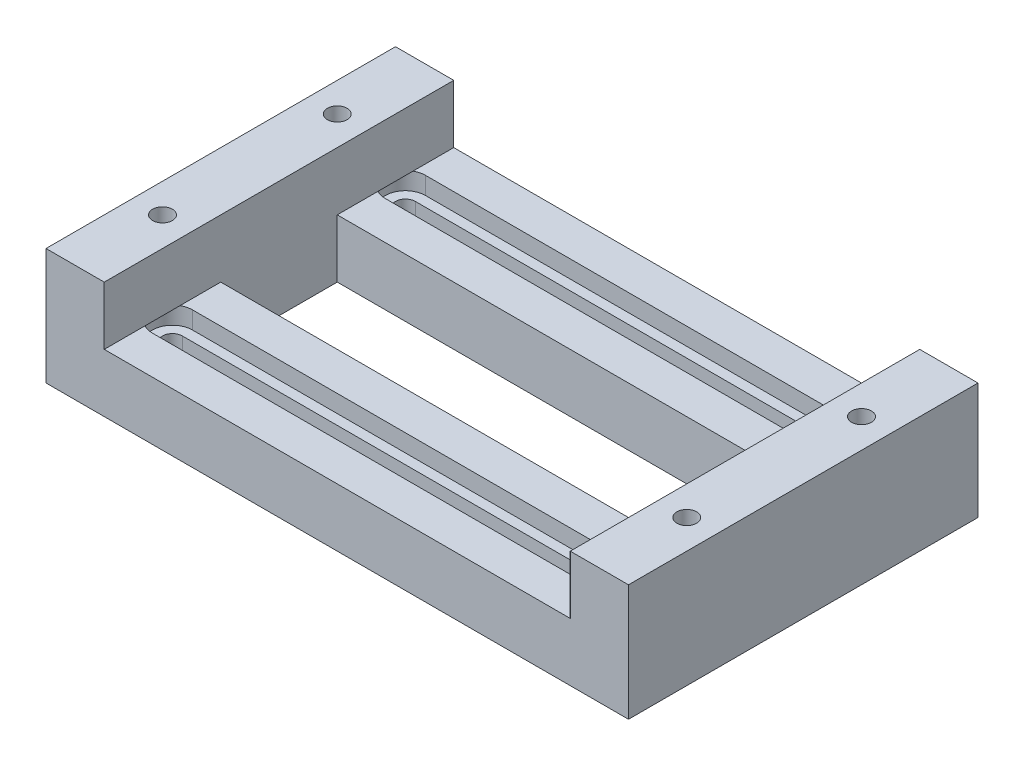
SolidWorks part; units mm, degrees
ref_plane "Front Plane" through (0, 0, 0) normal (0, 0, 1) x (1, 0, 0)
ref_plane "Top Plane" through (0, 0, 0) normal (0, 1, 0) x (1, 0, 0)
ref_plane "Right Plane" through (0, 0, 0) normal (1, 0, 0) x (0, 0, -1)
sketch "Sketch1" plane through (0, 0, 0) normal (0, 1, 0) x (1, 0, 0)
  line L0 (10, 40) -> (10, 20)
  line L1 (0, 0) -> (100, 0)
  line L2 (0, 0) -> (0, 60)
  line L3 (0, 60) -> (100, 60)
  line L4 (100, 0) -> (100, 60)
  line L5 (10, 20) -> (90, 20)
  line L6 (90, 20) -> (90, 40)
  line L7 (90, 40) -> (10, 40)
  line L8 (11.7, 10) -> (88.3, 10) construction
  line L9 (11.7, 11.7) -> (88.3, 11.7)
  line L10 (11.7, 8.3) -> (88.3, 8.3)
  line L11 (88.3, 50) -> (11.7, 50) construction
  line L12 (88.3, 48.3) -> (11.7, 48.3)
  line L13 (50, 0) -> (50, 20) construction
  line L14 (50, 40) -> (50, 60)
  line L15 (88.3, 51.7) -> (11.7, 51.7)
  circle A7 centre (5, 45) radius 1.7
  arc A22 (11.7, 11.7) -> (11.7, 8.3) centre (11.7, 10) ccw
  arc A23 (88.3, 8.3) -> (88.3, 11.7) centre (88.3, 10) ccw
  arc A24 (88.3, 48.3) -> (88.3, 51.7) centre (88.3, 50) ccw
  arc A25 (11.7, 51.7) -> (11.7, 48.3) centre (11.7, 50) ccw
  circle A29 centre (5, 15) radius 1.7
  circle A46 centre (95, 45) radius 1.7
  circle A47 centre (95, 15) radius 1.7
  point P14 (50, 50)
  point P17 (50, 10)
  point P22 (50, 50)
  point P33 (50, 10)
  point P34 (90, 10)
  point P35 (10, 10)
  point P36 (90, 50)
  point P37 (10, 50)
  dimension "D25" = 3.4
  dimension "D4" = 3.4
  dimension "D18" = 3.4
  dimension "D19" = 3.4
  dimension "D1" = 60
  dimension "D2" = 100
  dimension "D3" = 10
  dimension "D22" = 20
  dimension "D23" = 20
  dimension "D24" = 10
  dimension "D28" = 15
  dimension "D5" = 15
  dimension "D6" = 5
  dimension "D8" = 5
  dimension "D9" = 15
  dimension "D13" = 5
  dimension "D16" = 5
  dimension "D17" = 15
  dimension "D7" = 3.4
  dimension "D10" = 3.4
  dimension "D11" = 80
  dimension "D12" = 80
extrude "Boss-Extrude1" add sketch "Sketch1" along normal blind 10 contours L1 L4 L3 L2 A47 A46 A29 A7 L7 L6 L5 L0 region at (75, 0, -58.8338)
sketch "Sketch3" plane through (0, 10, 0) normal (0, 1, 0) x (1, 0, 0)
  line L4 (88.3, 53.45) -> (11.7, 53.45)
  line L5 (11.7, 46.55) -> (88.3, 46.55)
  line L6 (88.3, 13.45) -> (11.7, 13.45)
  line L7 (11.7, 6.55) -> (88.3, 6.55)
  line L8 (88.3, 13.45) -> (11.7, 13.45)
  line L9 (11.7, 6.55) -> (88.3, 6.55)
  line L10 (88.3, 53.45) -> (11.7, 53.45)
  line L11 (11.7, 46.55) -> (88.3, 46.55)
  arc A4 (88.3, 46.55) -> (88.3, 53.45) centre (88.3, 50) ccw
  arc A5 (11.7, 53.45) -> (11.7, 46.55) centre (11.7, 50) ccw
  arc A6 (11.7, 13.45) -> (11.7, 6.55) centre (11.7, 10) ccw
  arc A7 (88.3, 6.55) -> (88.3, 13.45) centre (88.3, 10) ccw
  arc A8 (11.7, 13.45) -> (11.7, 6.55) centre (11.7, 10) ccw
  arc A9 (88.3, 6.55) -> (88.3, 13.45) centre (88.3, 10) ccw
  arc A10 (88.3, 46.55) -> (88.3, 53.45) centre (88.3, 50) ccw
  arc A11 (11.7, 53.45) -> (11.7, 46.55) centre (11.7, 50) ccw
  dimension "D1" = 1.75
  dimension "D2" = 1.75
extrude "Cut-Slot insets" cut sketch "Sketch3" against normal blind 3
sketch "Sketch5" plane through (0, 10, 0) normal (0, 1, 0) x (1, 0, 0)
  line L2 (0, 60) -> (100, 60) construction
  line L3 (10, 60) -> (0, 60)
  line L4 (0, 60) -> (0, 0)
  line L5 (0, 0) -> (10, 0)
  line L6 (0, 0) -> (100, 0) construction
  line L9 (90, 0) -> (100, 0)
  line L10 (100, 0) -> (100, 60)
  line L11 (100, 60) -> (90, 60)
  line L20 (90, 60) -> (90, 0)
  line L21 (90, 20) -> (90, 40) construction
  line L22 (10, 0) -> (10, 60)
  line L23 (10, 40) -> (10, 20) construction
  circle A0 centre (95, 45) radius 1.7
  circle A3 centre (95, 15) radius 1.7
  circle A5 centre (5, 15) radius 1.7
  circle A8 centre (5, 45) radius 1.7
  circle A9 centre (5, 15) radius 1.7 construction
  circle A10 centre (5, 45) radius 1.7 construction
  circle A11 centre (95, 45) radius 1.7 construction
  circle A12 centre (95, 15) radius 1.7 construction
extrude "Boss-Extrude3" add sketch "Sketch5" along normal blind 10
sketch "Sketch6" plane through (0, 0, 0) normal (0, -1, 0) x (1, 0, 0)
  circle A0 centre (5, -45) radius 3.75
  circle A2 centre (5, -15) radius 3.75
  circle A3 centre (95, -15) radius 3.75
  circle A5 centre (95, -45) radius 3.75
  dimension "D1" = 7.5
  dimension "D3" = 7.5
  dimension "D4" = 7.5
  dimension "D6" = 7.5
extrude "Cut-Extrude1" cut sketch "Sketch6" against normal blind 2.5
chamfer "Chamfer1" distance 0.5 angle 45 8 edges at (50, 0, -51.7) (90, 0, -50) (10, 0, -50) (50, 0, -48.3) (50, 0, -8.3) (10, 0, -10) (90, 0, -10) (50, 0, -11.7)
chamfer "Chamfer2" distance 2 angle 45 4 edges at (95, 2.5, -18.75) (95, 2.5, -48.75) (5, 2.5, -48.75) (5, 2.5, -18.75)
equation "\"boltdiameter\"=3.4"
equation "\"D25@Sketch1\"=\"boltdiameter\""
equation "\"D4@Sketch1\"=\"boltdiameter\""
equation "\"D18@Sketch1\"=\"boltdiameter\""
equation "\"D19@Sketch1\"=\"boltdiameter\""
equation "\"boltfacediameter\"=7"
equation "\"boltFaceOffset\"= 1.75"
equation "\"D1@Sketch3\" = \"boltFaceOffset\""
equation "\"D2@Sketch3\" = \"boltFaceOffset\""
equation "\"screwInset\"=7.5"
equation "\"D1@Sketch6\"=\"screwInset\""
equation "\"D3@Sketch6\"=\"screwInset\""
equation "\"D4@Sketch6\"=\"screwInset\""
equation "\"D6@Sketch6\"=\"screwInset\""
equation "\"D7@Sketch1\"=\"boltdiameter\""
equation "\"D10@Sketch1\"=\"boltdiameter\""
equation "\"slotLength\"=80"
equation "\"D11@Sketch1\"=\"slotLength\""
equation "\"D12@Sketch1\"=\"slotLength\""
